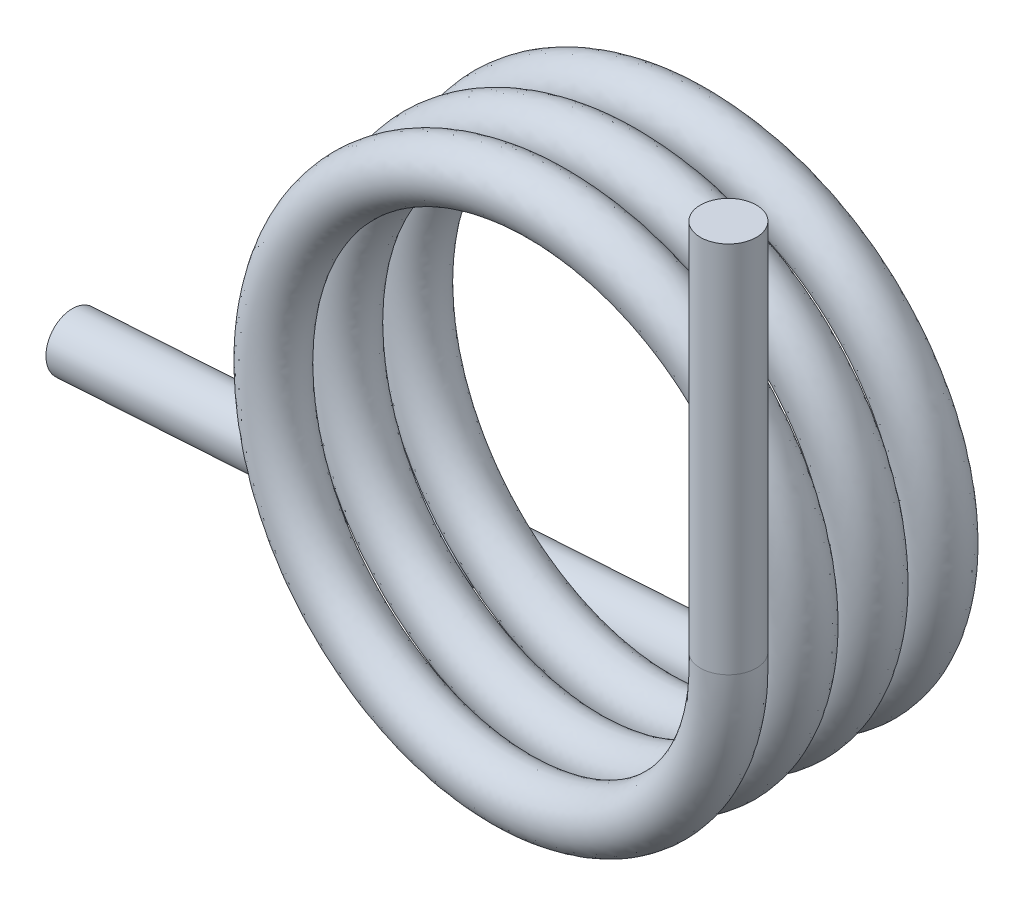
SolidWorks part; units mm, degrees
note: '?' marks a value the reader was unsure of.
ref_plane "Front" through (0, 0, 0) normal (0, 0, 1) x (1, 0, 0)
ref_plane "Top" through (0, 0, 0) normal (0, 1, 0) x (1, 0, 0)
ref_plane "Right" through (0, 0, 0) normal (1, 0, 0) x (0, 0, -1)
sketch "Sketch1" plane through (0, 0, 0) normal (0, 0, 1) x (1, 0, 0)
  circle A0 centre (0, 0) radius 2.625
  circle A1 centre (0, 0) radius 2.25 construction
  circle A2 centre (0, 2.625) radius 0.375 construction
  dimension "D1" = 0.75
  dimension "D2" = 4.5
curve "Helix/Spiral1" pitch 0.75 height 2.43 turns 3.24
sketch "Sketch2" plane through (0, 0, 0) normal (0, 1, 0) x (1, 0, 0)
  circle A0 centre (2.625, 0) radius 0.3
  dimension "D1" = 0.6
sweep "Sweep1" add profiles "Sketch2" path "Helix/Spiral1"
sketch "Sketch4" plane through (0, 0, 0) normal (-0.998, -0.0628, 0) x (0.0628, -0.998, 0)
  circle A7 centre (2.625, -2.4303) radius 0.3
  circle A11 centre (2.625, -2.4303) radius 0.3
  dimension "D1" = 0
extrude "Boss-Extrude1" add sketch "Sketch4" along normal blind 7
sketch "Sketch5" plane through (0, 0, 0) normal (0, 1, 0) x (1, 0, 0)
  circle A5 centre (2.625, 0) radius 0.3
  circle A9 centre (2.625, 0) radius 0.3
  dimension "D1" = 0
extrude "Boss-Extrude2" add sketch "Sketch5" along normal blind 4
ref_axis "Axis2" through (-6.8589, -3.0617, -2.4303) along (0.998, 0.0628, 0)?
ref_axis "Axis1" through (2.625, 4, 0) along (0, -1, 0)?
sketch "Sketch11" plane through (0, 0, 0) normal (1, 0, 0) x (0, 0, -1)
  line L0 (0, 0) -> (2.4303, 0)
  line L1 (2.4303, -3.0617) -> (2.4303, -2.6169) construction
  line L2 (1.2152, 0) -> (1.2152, 5.2574)
  line L3 (2.4303, -2.063) -> (2.4303, 0) construction
ref_plane "Plane1" through (0, 0, -1.2152) normal (0, 0, 1) x (1, 0, 0)
ref_plane "Plane2" through (0, 0, -1.2152) normal (0, 0, 1) x (1, 0, 0)
